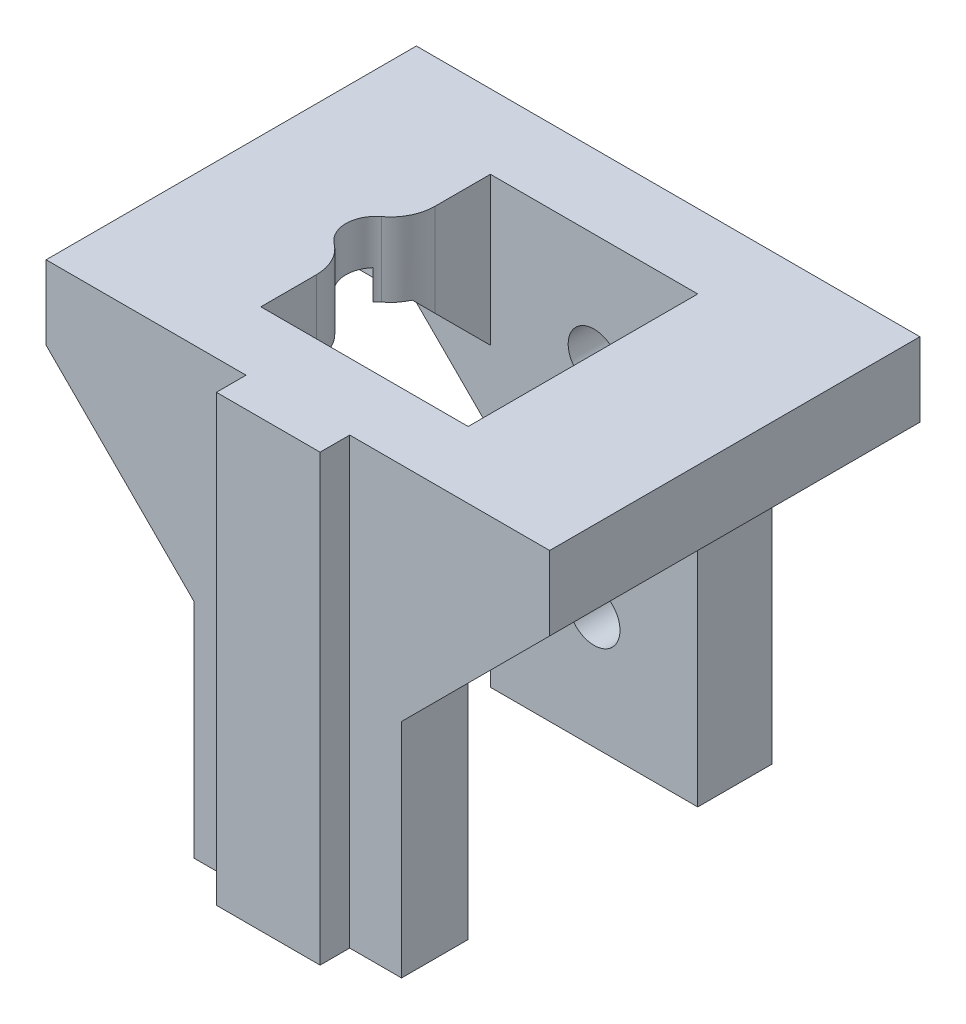
SolidWorks part; units mm, degrees
ref_plane "Top Plane" through (0, 0, 0) normal (0, 0, 1) x (1, 0, 0)
ref_plane "Right Plane" through (0, 0, 0) normal (0, 1, 0) x (1, 0, 0)
ref_plane "Front Plane" through (0, 0, 0) normal (1, 0, 0) x (0, 0, -1)
sketch "Sketch1" plane through (0, 0, 0) normal (0, 0, 1) x (1, 0, 0)
  line L0 (0, 24.45) -> (0, 30)
  line L1 (0, 0) -> (7, 0)
  line L2 (0, 0) -> (0, 5.95)
  line L4 (7, 0) -> (7, 25)
  line L5 (0, 30) -> (17, 30)
  line L7 (7, 25) -> (17, 25)
  line L8 (17, 30) -> (17, 25)
  line L9 (0, 9.45) -> (0, 20.95)
  arc A0 (0, 5.95) -> (0, 9.45) centre (0, 7.7) ccw
  arc A1 (0, 20.95) -> (0, 24.45) centre (0, 22.7) ccw
  dimension "D5" = 3.5
  dimension "D1" = 30
  dimension "D2" = 10
  dimension "D3" = 7
  dimension "D4" = 5
  dimension "D6" = 15
  dimension "D7" = 7.3
extrude "Boss-Extrude1" add sketch "Sketch1" along normal blind 5
sketch "Sketch2" plane through (0, 0, 5) normal (0, 0, 1) x (1, 0, 0)
  line L1 (7, 25) -> (17, 25)
  line L2 (7, 25) -> (7, 30)
  line L3 (7, 30) -> (17, 30)
  line L4 (17, 25) -> (17, 30)
extrude "Boss-Extrude2" add sketch "Sketch2" along normal blind 15.5
sketch "Sketch3" plane through (0, 0, 20.5) normal (0, 0, 1) x (1, 0, 0)
  line L0 (7, 0) -> (7, 25)
  line L1 (17, 30) -> (0, 30)
  line L2 (17, 30) -> (17, 25)
  line L3 (7, 0) -> (0, 0)
  line L4 (0, 30) -> (0, 0)
  line L5 (7, 25) -> (17, 25)
extrude "Boss-Extrude3" add sketch "Sketch3" along normal blind 6.5
chamfer "Chamfer1" distance 10 angle 45 2 edges at (7, 25, 2.5) (7, 25, 23.75)
chamfer "Chamfer2" distance 5 angle 45 2 edges at (12, 25, 5) (12, 25, 20.5)
sketch "Sketch4" plane through (0, 25, 0) normal (0, -1, 0) x (1, 0, 0)
  line L0 (17, 15.5) -> (7, 10) construction
  circle A0 centre (12, 12.75) radius 3.75
  dimension "D1" = 7.5
extrude "Cut-Extrude1" cut sketch "Sketch4" against normal blind 2 and the other way blind 5
mirror "Mirror1" about plane through (0, 30, 27) normal (1, 0, 0) of bodies 105
sketch "Sketch5" plane through (0, 0, 27) normal (0, 0, 1) x (1, 0, 0)
  line L0 (-7, 0) -> (7, 0) construction
  line L1 (-17, 30) -> (-3.5, 30)
  line L2 (-17, 30) -> (-17, 0)
  line L3 (-17, 0) -> (-3.5, 0)
  line L4 (-3.5, 30) -> (-3.5, 0)
  line L6 (17, 30) -> (3.5, 30)
  line L7 (17, 30) -> (17, 0)
  line L8 (17, 0) -> (3.5, 0)
  line L9 (3.5, 30) -> (3.5, 0)
  dimension "D1" = 7
extrude "Cut-Extrude2" cut sketch "Sketch5" against normal blind 2
chamfer "Chamfer3" distance 1.5 angle 45 2 edges at (1.75, 22.7, 0) (1.75, 7.7, 0)
sketch "Sketch6" plane through (0, 30, 0) normal (0, 1, 0) x (1, 0, 0)
  line L0 (-7, -20.5) -> (-7, -5) construction
  circle A0 centre (-7, -12.75) radius 2
  dimension "D1" = 4
extrude "Cut-Extrude4" cut sketch "Sketch6" against normal through all
fillet "Fillet1" radius 3 2 edges at (-7, 27.5, 14.75) (-7, 27.5, 10.75)
